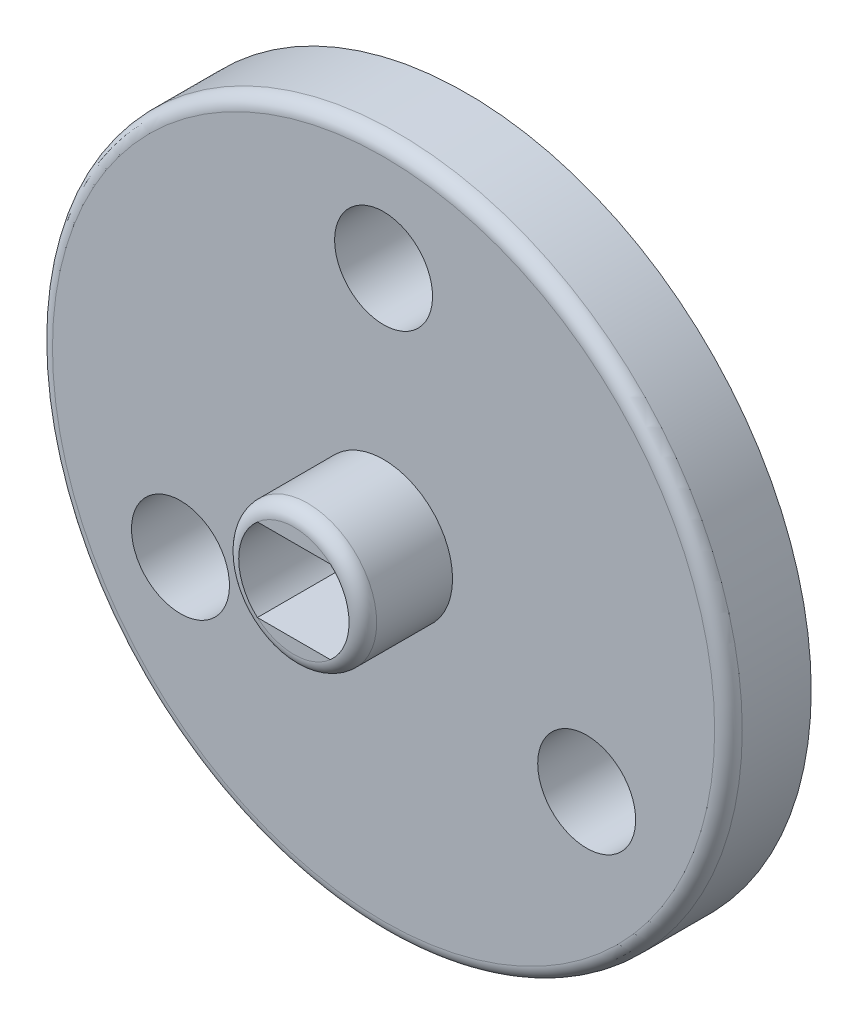
SolidWorks part; units mm, degrees
ref_plane "Ebene vorne" through (0, 0, 0) normal (0, 0, 1) x (1, 0, 0)
ref_plane "Ebene oben" through (0, 0, 0) normal (0, 1, 0) x (1, 0, 0)
ref_plane "Ebene rechts" through (0, 0, 0) normal (1, 0, 0) x (0, 0, -1)
sketch "Skizze1" plane through (0, 0, 0) normal (1, 0, 0) x (0, 0, -1)
  line L1 (96.5, 25) -> (96.5, 0) construction
  line L2 (90.5, 25) -> (90.5, 0) construction
  line L3 (0, 25) -> (99, 25) construction
  line L5 (96.5, 25) -> (96.5, 0)
  line L6 (90.5, 25) -> (90.5, 5)
  line L7 (90.5, 25) -> (96.5, 25)
  line L8 (84, 4) -> (84, 0) construction
  line L10 (84, 4) -> (84, 0)
  line L12 (0, 0) -> (99, 0) construction
  line L13 (84, 0) -> (96.5, 0)
  line L14 (84, 5) -> (84, 4) construction
  line L15 (90.5, 5) -> (84, 5) construction
  line L16 (84, 5) -> (84, 4)
  line L17 (90.5, 5) -> (84, 5)
revolve "Rotation1" add sketch "Skizze1" angle 360 about L13
sketch "Skizze2" plane through (0, 0, -96.5) normal (0, 0, -1) x (-1, 0, 0)
  line L0 (0, 0) -> (25, 0) construction
  line L1 (0, 0) -> (-450, 0) construction
  line L2 (2.6458, 3) -> (-2.6458, 3) construction
  line L3 (0, 0) -> (4, 0)
  line L4 (0, 0) -> (-4, 0)
  line L5 (2.6458, 3) -> (-2.6458, 3)
  arc A1 (-2.6458, 3) -> (-4, 0) centre (0, 0) ccw construction
  arc A2 (4, 0) -> (2.6458, 3) centre (0, 0) ccw construction
  arc A3 (-2.6458, 3) -> (-4, 0) centre (0, 0) ccw
  arc A4 (4, 0) -> (2.6458, 3) centre (0, 0) ccw
extrude "Schnitt-Linear austragen1" cut sketch "Skizze2" against normal through all
mirror "Spiegeln1" about plane through (0, 0, -84) normal (0, -1, 0) of "Schnitt-Linear austragen1"
sketch "Skizze3" plane through (0, 0, -96.5) normal (0, 0, -1) x (-1, 0, 0)
  circle A0 centre (0, 0) radius 17 construction
  point P4 (0, 17)
hole_wizard "Ø7.1 (7.1) Durchmesser Bohrung1" positions "Skizze3" profile "Skizze4" hole size "Ø7.1" standard "DIN"
sketch "Skizze4" plane through (0, 17, -96.5) normal (1, 0, 0) x (0, 1, 0)
  line L0 (0, 0) -> (0, 10.6331)
  line L1 (0, 10.6331) -> (3.55, 8.5)
  line L2 (3.55, 8.5) -> (3.55, 0)
  line L5 (3.55, 0) -> (0, 0)
  line L10 (0, 10.6331) -> (-3.55, 8.5) construction
  line L11 (0, -6.35) -> (0, 107.95) construction
  dimension "Bohrerdurchmesser" = 7.1
  dimension "Bohrungstiefe" = 8.5
  dimension "Spitzenwinkel" = 118
pattern_circular "Kreismuster1" count 3 over 360 of "Ø7.1 (7.1) Durchmesser Bohrung1" reverse direction yes
fillet "Verrundung1" radius 1 2 edges at (5, 0, -84) (25, 0, -90.5)
